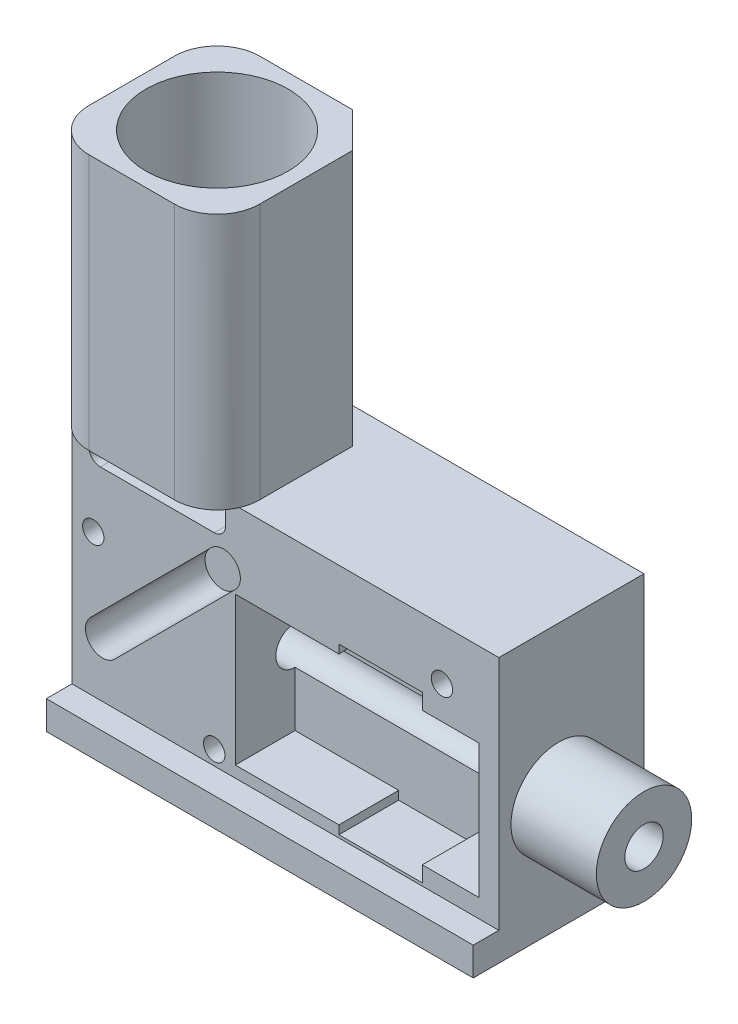
SolidWorks part; units mm, degrees
ref_plane "Front Plane" through (0, 0, 0) normal (0, 0, 1) x (1, 0, 0)
ref_plane "Top Plane" through (0, 0, 0) normal (0, 1, 0) x (1, 0, 0)
ref_plane "Right Plane" through (0, 0, 0) normal (1, 0, 0) x (0, 0, -1)
sketch "Sketch1" plane through (0, 0, 0) normal (0, 1, 0) x (1, 0, 0)
  line L1 (7.5, 3) -> (-7.5, 3)
  line L2 (7.5, 3) -> (7.5, -3)
  line L3 (7.5, -3) -> (-7.5, -3)
  line L4 (-7.5, 3) -> (-7.5, -3)
  line L5 (7.5, 3) -> (-7.5, -3) construction
  line L6 (7.5, -3) -> (-7.5, 3) construction
  point P0 (0, 0)
  dimension "D1" = 6
  dimension "D2" = 15
extrude "Main Body Ext" add sketch "Sketch1" along normal blind 9.3
sketch "Sketch8" plane through (0, 9.3, 0) normal (0, 1, 0) x (1, 0, 0)
  line L0 (-2.75, 3) -> (-1.5, 1.75)
  line L1 (-2.75, 3) -> (-7.5, 3)
  line L2 (-1.5, 1.75) -> (-1.5, -3)
  line L3 (-1.5, -3) -> (-7.5, -3)
  line L4 (-7.5, 3) -> (-7.5, -3)
  line L5 (-2.125, 2.375) -> (-7.5, -3) construction
  line L6 (-1.5, -3) -> (-7.5, 3) construction
  line L7 (-7.5, 3) -> (-7.5, -3) construction
  line L8 (0, 0) -> (-4.5, 0) construction
  point P0 (-4.5, 0)
  dimension "D1" = 6
  dimension "D2" = 6
  dimension "D3" = 1.25
  dimension "D4" = 3
extrude "Emission Path Ext" add sketch "Sketch8" along normal blind 9
sketch "Sketch3" plane through (0, 0, 0) normal (0, -1, 0) x (1, 0, 0)
  line L0 (-7.5, -3) -> (-7.5, 3) construction
  line L1 (0, 0) -> (-4.5, 0) construction
  circle A0 centre (-4.5, 0) radius 1.25
  dimension "D1" = 3
  dimension "D2" = 2.5
extrude "Emission and Grin Cut" cut sketch "Sketch3" against normal through all
sketch "Sketch4" plane through (7.5, 0, 0) normal (1, 0, 0) x (0, 0, -1)
  line L1 (-3, 0) -> (3, 0) construction
  circle A0 centre (0, 4) radius 0.675
  dimension "D1" = 1.35
  dimension "D2" = 4
extrude "Fiber Ferrule Cut" cut sketch "Sketch4" against normal offset from surface (13 mm away) 2 up to face at (-7.5, 9.15, 0)
sketch "Sketch41" plane through (7.5, 0, 0) normal (1, 0, 0) x (0, 0, -1)
  circle A0 centre (0, 4) radius 1.675
  circle A1 centre (0, 4) radius 0.675 construction
  circle A2 centre (0, 4) radius 0.675
  dimension "D1" = 1
extrude "Fiber Ferrule Port Ext" add sketch "Sketch41" along normal blind 3
sketch "Sketch5" plane through (0, 0, 3) normal (0, 0, 1) x (1, 0, 0)
  line L0 (-7.5, 0) -> (7.5, 0) construction
  line L1 (7.5, 9.3) -> (-7.5, 9.3)
  line L2 (7.5, 9.3) -> (7.5, 1)
  line L3 (7.5, 1) -> (-7.5, 1)
  line L4 (-7.5, 9.3) -> (-7.5, 1)
  line L5 (7.5, 9.3) -> (-7.5, 1) construction
  line L6 (7.5, 1) -> (-7.5, 9.3) construction
  line L7 (-1.5, 9.3) -> (7.5, 9.3) construction
  line L9 (7.5, 9.3) -> (7.5, 0) construction
  line L10 (-7.5, 18.3) -> (-7.5, 0) construction
  point P0 (0, 5.15)
  dimension "D1" = 1
extrude "FilterSet Cut1" cut sketch "Sketch5" against normal blind 0.9
sketch "Sketch6" plane through (0, 0, 2.1) normal (0, 0, 1) x (1, 0, 0)
  line L0 (3.4, 7.5) -> (3.4, 1.5)
  line L1 (3.4, 1.5) -> (-0.9, 1.5)
  line L3 (-7.5, 1) -> (7.5, 1) construction
  line L4 (-7.5, 9.3) -> (-7.5, 1) construction
  line L5 (-6.9, 8.9) -> (-6.9, 8.5)
  line L7 (-1.5, 9.3) -> (-7.5, 9.3) construction
  line L8 (-2.1, 8.9) -> (-2.1, 8.5)
  line L9 (-6, 2.5) -> (-6, 1) construction
  line L10 (-2.5, 9.3) -> (-6.5, 9.3)
  line L11 (-4.5, 4) -> (-4.5, 1) construction
  line L12 (-4.5, 4) -> (0.4851, 4) construction
  line L13 (-2.5, 8.1) -> (-6.5, 8.1)
  line L14 (-0.9, 1.5) -> (-0.9, 7.5)
  line L15 (-2.5, 9.3) -> (-6.5, 8.1) construction
  line L16 (-2.5, 8.1) -> (-6.5, 9.3) construction
  line L18 (-2.6059, 7.5912) -> (-6.8485, 3.3485)
  line L20 (-1.7574, 6.7426) -> (-6, 2.5)
  line L21 (-2.6059, 7.5912) -> (-6, 2.5) construction
  line L22 (-6.8485, 3.3485) -> (-1.7574, 6.7426) construction
  line L24 (-0.9, 7.5) -> (3.4, 7.5)
  line L33 (-2.5, 9.3) -> (1.102, 9.3) construction
  line L35 (1.102, 8.1) -> (-2.5, 8.1) construction
  line L36 (-6.5, 8.1) -> (-4.098, 8.1) construction
  line L38 (-4.098, 9.3) -> (-6.5, 9.3) construction
  arc A0 (-2.5, 9.3) -> (-2.1, 8.9) centre (-2.5, 8.9) cw
  arc A2 (-6.5, 9.3) -> (-6.9, 8.9) centre (-6.5, 8.9) ccw
  arc A3 (-2.6059, 7.5912) -> (-1.7574, 6.7426) centre (-2.1816, 7.1669) cw
  arc A5 (-6.8485, 3.3485) -> (-6, 2.5) centre (-6.4243, 2.9243) ccw
  arc A7 (-6.5, 8.1) -> (-6.9, 8.5) centre (-6.5, 8.5) cw
  arc A8 (-2.5, 8.1) -> (-2.1, 8.5) centre (-2.5, 8.5) ccw
  point P5 (-4.5, 8.7)
  point P10 (-4.3029, 5.0456)
  point P24 (-0.6861, 4)
  point P48 (-0.9, 4.5)
  line M12 (-1.5, 9.3) -> (-7.5, 9.3)
  dimension "D10" = 1.5
  dimension "D5" = 6.6
  dimension "D8" = 0.5
  dimension "D11" = 0.4
  dimension "D12" = 0.4
  dimension "D2" = 45
  dimension "D3" = 6
  dimension "D4" = 1.2
  dimension "D6" = 3
  dimension "D7" = 4
  dimension "D9" = 3
  dimension "D13" = 1.2
  dimension "D14" = 3
  dimension "D15" = 6
  dimension "D17" = 4.3
extrude "FilterSet Cut2" cut sketch "Sketch6" against normal offset from surface (4.2 mm away) 0.9 contours L18 A5 L20 A3 | L13 A8 L8 A0 A2 L5 A7 M12 region at (-4.5, 8.7, 2.1) region at (-4.3029, 5.0456, 2.1) up to face at (-0.0625, 9.95, -3)
sketch "Sketch39" plane through (0, 0, 0) normal (0, 0, 1) x (1, 0, 0)
  line L0 (-4.5, 4) -> (0.4851, 4) construction
  line L1 (-4.5, 4) -> (-0.9, 4) construction
  line L2 (0.6, 6.6) -> (1.88, 6.6)
  line L3 (1.88, 6.6) -> (1.88, 6.9)
  line L5 (3.4, 7.5) -> (3.4, 1.5) construction
  line L6 (3.4, 6.9) -> (4.81, 6.9)
  line L8 (4.81, 4) -> (3.4, 4)
  line L10 (3.4, 6.9) -> (1.88, 6.9)
  line L12 (3.4, 4) -> (-0.4058, 4)
  line L16 (-0.9, 6.6) -> (-1.76, 6.6)
  line L17 (-1.76, 6.6) -> (-1.76, 4)
  line L18 (-1.76, 4) -> (-0.9, 4)
  line L19 (-0.9, 6.6) -> (0.6, 6.6)
  line L22 (-0.5058, 4) -> (0.4851, 4) construction
  line L23 (-0.9, 4) -> (-0.4058, 4)
  line L24 (4.81, 4) -> (6.967, 4) construction
  line L26 (4.81, 4) -> (4.81, 6.9) construction
  line L27 (4.81, 4) -> (6.81, 4)
  line L30 (6.81, 4) -> (6.81, 6.35)
  line L31 (6.81, 6.35) -> (4.81, 6.35)
  line L32 (4.81, 6.35) -> (4.81, 6.9)
  dimension "D1" = 2.93
  dimension "D3" = 2.6
  dimension "D4" = 6.57
  dimension "D5" = 0.55
  dimension "D6" = 2
  dimension "D7" = 2.74
  dimension "D8" = 2.9
sketch "Sketch10" plane through (0, 18.3, 0) normal (0, 1, 0) x (1, 0, 0)
  line L0 (-4.5, 0) -> (-4.5, -3) construction
  line L1 (-7.5, -3) -> (-1.5, -3) construction
  line L3 (-4.5, 0) -> (-7.5, 0) construction
  line L4 (-7.5, 3) -> (-7.5, -3) construction
  circle A0 centre (-4.5, 0) radius 2.5
  dimension "D1" = 5
extrude "Emission Lens Cut" cut sketch "Sketch10" against normal offset from surface (8.5 mm away) 0.5 up to face at (-4.125, 9.3, 1.3313)
sketch "Sketch44" plane through (0, 0, 0) normal (0, 0, 1) x (1, 0, 0)
  line L1 (3.4, 1.1) -> (1.88, 1.1)
  line L2 (4.81, 1.1) -> (3.4, 1.1)
  line L3 (4.81, 1.65) -> (4.81, 1.1)
  line L4 (6.81, 1.65) -> (4.81, 1.65)
  line L5 (-0.9, 1.4) -> (-1.76, 1.4)
  line L6 (0.6, 1.4) -> (-0.9, 1.4)
  line L7 (0.6, 1.4) -> (1.88, 1.4)
  line L8 (1.88, 1.4) -> (1.88, 1.1)
  line L14 (0.6, 6.6) -> (-0.9, 6.6)
  line L15 (-0.9, 6.6) -> (-1.76, 6.6)
  line L16 (-1.76, 6.6) -> (-1.76, 4)
  line L17 (-1.76, 4) -> (-0.9, 4)
  line L18 (-0.9, 4) -> (-0.4058, 4)
  line L19 (-0.4058, 4) -> (3.4, 4)
  line L20 (3.4, 4) -> (4.81, 4)
  line L21 (4.81, 4) -> (6.81, 4)
  line L22 (6.81, 4) -> (6.81, 6.35)
  line L23 (6.81, 6.35) -> (4.81, 6.35)
  line L24 (4.81, 6.35) -> (4.81, 6.9)
  line L25 (4.81, 6.9) -> (3.4, 6.9)
  line L26 (3.4, 6.9) -> (1.88, 6.9)
  line L27 (1.88, 6.9) -> (1.88, 6.6)
  line L28 (0.6, 6.6) -> (-0.9, 6.6)
  line L29 (-0.9, 6.6) -> (-1.76, 6.6)
  line L30 (-1.76, 6.6) -> (-1.76, 1.4)
  line L31 (-1.76, 4) -> (-0.9, 4) construction
  line L32 (-0.9, 4) -> (-0.4058, 4) construction
  line L33 (-0.4058, 4) -> (3.4, 4) construction
  line L34 (3.4, 4) -> (4.81, 4) construction
  line L35 (4.81, 4) -> (6.81, 4) construction
  line L36 (6.81, 1.65) -> (6.81, 6.35)
  line L37 (6.81, 6.35) -> (4.81, 6.35)
  line L38 (4.81, 6.35) -> (4.81, 6.9)
  line L39 (4.81, 6.9) -> (3.4, 6.9)
  line L40 (3.4, 6.9) -> (1.88, 6.9)
  line L50 (1.88, 6.9) -> (1.88, 6.6)
  line L51 (1.88, 6.6) -> (0.6, 6.6)
  line L52 (1.88, 6.6) -> (0.6, 6.6)
  dimension "D1" = 0
extrude "Excitation Pathway Cut 2" cut sketch "Sketch44" along normal up to surface (2.1 mm away) up to face at (-2.8846, 7.6538, 2.1)
sketch "Sketch15" plane through (0, 0, 0) normal (0, -1, 0) x (1, 0, 0)
  line L0 (-6.25, 1.875) -> (-6.25, -1.875) construction
  line L2 (-1.5, 0) -> (-4.5, 0) construction
  line L3 (-4.5, 0) -> (-6.25, 0) construction
  circle A0 centre (-6.25, -1.875) radius 0.795
  circle A1 centre (-6.25, 1.875) radius 0.795
  circle A2 centre (-1.5, 0) radius 0.795
  dimension "D4" = 1.59
  dimension "D1" = 3.75
  dimension "D2" = 3
  dimension "D3" = 1.75
extrude "Magnets Cut" cut sketch "Sketch15" against normal blind 0.9
sketch "Sketch18" plane through (0, 0, 2.1) normal (0, 0, 1) x (1, 0, 0)
  line L0 (-7.5, 9.3) -> (-7.5, 1) construction
  line L1 (7.5, 1) -> (7.5, 9.3) construction
  line L2 (7.5, 9.3) -> (-1.5, 9.3) construction
  line L3 (-7.5, 0) -> (7.5, 0) construction
  line L7 (-7.5, 1) -> (7.5, 1) construction
  line L9 (-7.5, 1) -> (-7.5, 0) construction
  circle A0 centre (-6.75, 6) radius 0.375
  circle A1 centre (5.5, 7.5) radius 0.375
  circle A2 centre (-2.5, 1.51) radius 0.375
  dimension "D1" = 0.75
  dimension "D2" = 0.75
  dimension "D3" = 1.8
  dimension "D4" = 2
  dimension "D5" = 5
  dimension "D6" = 1.51
  dimension "D7" = 5
extrude "Screw Holes Cut" cut sketch "Sketch18" against normal blind 3 and the other way through all
fillet "External Fillet 1" radius 1.5 2 edges at (-7.5, 9.15, -3)
sketch "Sketch14" plane through (0, 0, 0) normal (0, -1, 0) x (1, 0, 0)
  line L1 (7.5, -3) -> (-6, -3) construction
  line L2 (1.5, -2.0099) -> (0.8399, -3)
  line L3 (7.5, -3) -> (-6, -3) construction
  line L4 (0.8399, -3) -> (1.5, -3)
  line L5 (1.5, -3) -> (-7.5, 3) construction
  line L6 (-7.5, -1.5) -> (-7.5, 3) construction
  line L7 (-7.5, 3) -> (7.5, 3) construction
  line L8 (3.5, -2.0099) -> (4.4901, -3)
  line L9 (1.5, -2.0099) -> (3.5, -2.0099)
  line L11 (1.5, -3) -> (3.3387, -3)
  line M3 (-6, -3) -> (7.5, -3)
  dimension "D1" = 9
  dimension "D2" = 1.19
  dimension "D3" = 45
  dimension "D4" = 2
sketch "Sketch28" plane through (0, 8.1, 0) normal (0, 1, 0) x (1, 0, 0)
  circle A0 centre (-4.5, 0) radius 1.5
  dimension "D1" = 3
extrude "Emission Pathway Cut" cut sketch "Sketch28" against normal blind 4 and the other way through all
extrude "Small Baseplate Cut" [suppressed] cut sketch "Sketch14" against normal blind 1.5 contours L5 L2 M3 | L5 L8 L9 L2 M3
sketch "Sketch36" plane through (0, 18.3, 0) normal (0, 1, 0) x (1, 0, 0)
  line L0 (-7.5, -1.5) -> (-7.5, -3)
  line L1 (-7.5, 1.5) -> (-7.5, -3) construction
  line L2 (-7.5, -3) -> (-6, -3)
  line L3 (-7.5, -3) -> (-3, -3) construction
  line L4 (-9.9, 0) -> (9.9, 0) construction
  arc A0 (-7.5, -1.5) -> (-6, -3) centre (-6, -1.5) ccw
  dimension "D1" = 1.5
  dimension "D2" = 1.5
  dimension "D3" = 3
extrude "Cut-Extrude16" cut sketch "Sketch36" against normal up to surface (9 mm away) up to face at (-4.4051, 9.3, 1.3006)
sketch "Sketch37" plane through (0, 9.8, 0) normal (0, 1, 0) x (1, 0, 0)
  circle A0 centre (-4.5, 0) radius 2
  circle A1 centre (-4.5, 0) radius 1.5 construction
  dimension "D1" = 4
extrude "Cut-Extrude17" cut sketch "Sketch37" against normal up to next
sketch "Sketch45" plane through (0, 0, 0) normal (0, -1, 0) x (1, 0, 0)
  line L0 (7.5, -3) -> (-7.5, 3) construction
  line L1 (7.5, -1.6639) -> (6.6093, -3)
  line L2 (7.5, 3) -> (7.5, -3) construction
  line L3 (7.5, -3) -> (-6, -3) construction
  dimension "D1" = 33.69
extrude "Baseplate Notch Cut" cut sketch "Sketch45" against normal blind 2 and the other way through all
